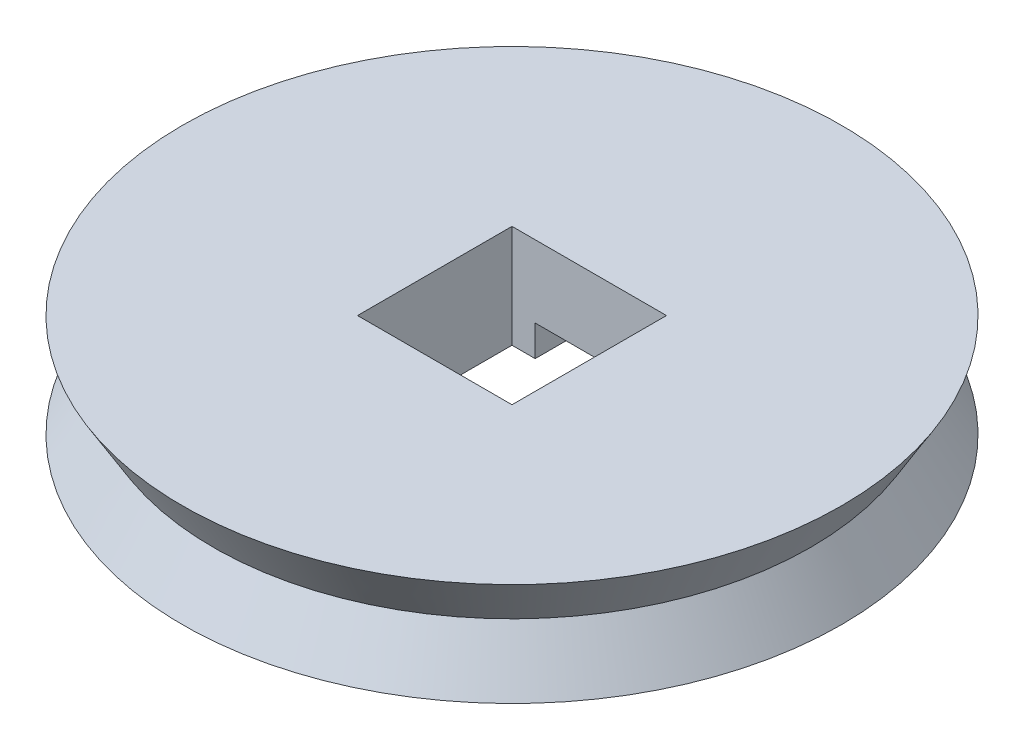
SolidWorks part; units mm, degrees
ref_plane "Front Plane" through (0, 0, 0) normal (0, 0, 1) x (1, 0, 0)
ref_plane "Top Plane" through (0, 0, 0) normal (0, 1, 0) x (1, 0, 0)
ref_plane "Right Plane" through (0, 0, 0) normal (1, 0, 0) x (0, 0, -1)
sketch "Sketch1" plane through (0, 0, 0) normal (0, 1, 0) x (1, 0, 0)
  circle A0 centre (0, 0) radius 32
  dimension "D1" = 64
extrude "Boss-Extrude1" add sketch "Sketch1" along normal blind 10
sketch "Sketch2" plane through (0, 0, 0) normal (0, 0, 1) x (1, 0, 0)
  line L0 (-32, 0) -> (32, 0) construction
  line L1 (32, 10) -> (-32, 10) construction
  line L2 (-32, 0) -> (32, 0) construction
  line L3 (32, 10) -> (-32, 10) construction
  line L4 (32, 10) -> (29, 5)
  line L5 (29, 5) -> (32, 0)
  line L6 (32, 0) -> (32, 10)
  point P6 (32, 5)
  dimension "D1" = 3
sweep "Cut-Sweep1" cut profiles "Sketch2" path "Sketch1<2>"
sketch "Sketch1<2>" plane through (0, 0, 0) normal (0, 1, 0) x (1, 0, 0) same geometry as "Sketch1"
sketch "Sketch3" plane through (0, 10, 0) normal (0, 1, 0) x (1, 0, 0)
  line L1 (-7.5, -7.5) -> (7.5, -7.5)
  line L2 (-7.5, -7.5) -> (-7.5, 7.5)
  line L3 (-7.5, 7.5) -> (7.5, 7.5)
  line L4 (7.5, -7.5) -> (7.5, 7.5)
  line L5 (-7.5, -7.5) -> (7.5, 7.5) construction
  line L6 (-7.5, 7.5) -> (7.5, -7.5) construction
  point P0 (0, 0)
  dimension "D1" = 15
  dimension "D2" = 15
extrude "Cut-Extrude1" cut sketch "Sketch3" against normal through all
sketch "Sketch4" plane through (0, 0, 0) normal (0, -1, 0) x (1, 0, 0)
  line L0 (-7.5, 7.5) -> (7.5, 7.5) construction
  line L1 (5.25, 7.5) -> (-5.25, 7.5)
  line L2 (5.25, 7.5) -> (5.25, 18)
  line L3 (5.25, 18) -> (-5.25, 18)
  line L4 (-5.25, 7.5) -> (-5.25, 18)
  line L5 (7.5, -7.5) -> (-7.5, -7.5) construction
  line L6 (5.25, -7.5) -> (-5.25, -7.5)
  line L7 (5.25, -7.5) -> (5.25, -18)
  line L8 (5.25, -18) -> (-5.25, -18)
  line L9 (-5.25, -7.5) -> (-5.25, -18)
  line L10 (-7.5, 0) -> (7.5, 0) construction
  line L11 (-7.5, -7.5) -> (-7.5, 7.5) construction
  line L12 (7.5, 7.5) -> (7.5, -7.5) construction
  line L13 (-7.5, 7.5) -> (7.5, 7.5) construction
  point P18 (-2.7928, -17.664)
  point P19 (0, 7.5)
  point P20 (0, 7.5)
  dimension "D1" = 10.5
  dimension "D2" = 10.5
extrude "Cut-Extrude2" cut sketch "Sketch4" against normal blind 3
